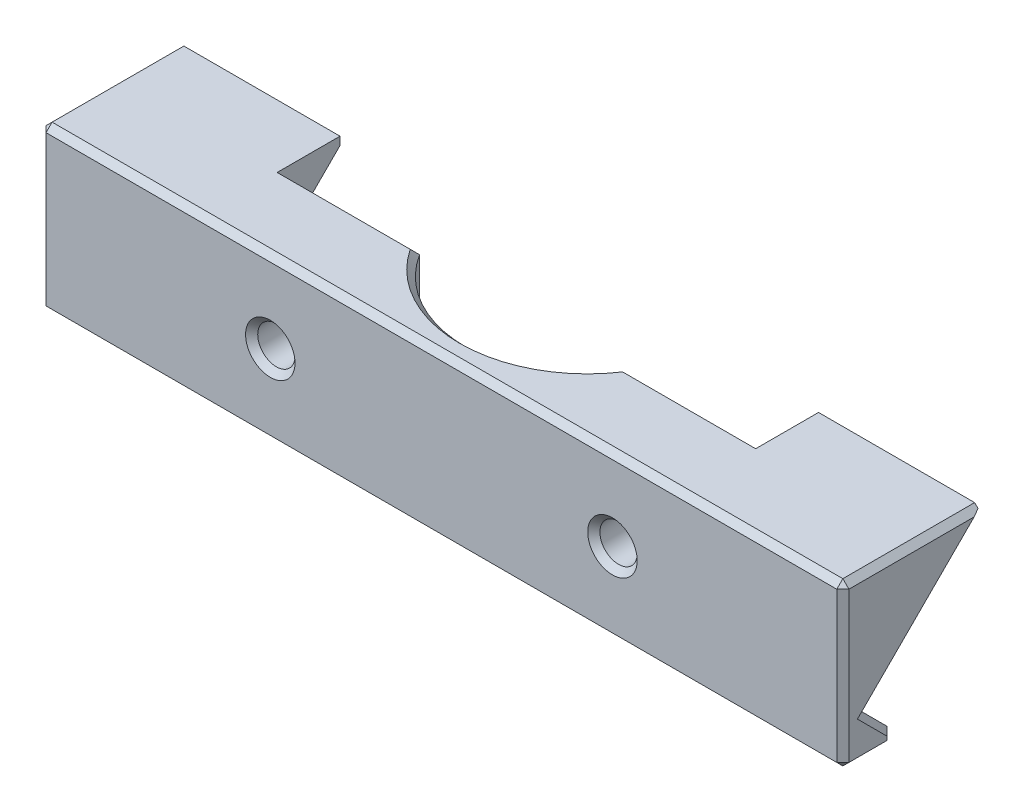
SolidWorks part; units mm, degrees
ref_plane "Front" through (0, 0, 0) normal (0, 0, 1) x (1, 0, 0)
ref_plane "Top" through (0, 0, 0) normal (0, 1, 0) x (1, 0, 0)
ref_plane "Right" through (0, 0, 0) normal (1, 0, 0) x (0, 0, -1)
sketch "Skizze1" plane through (0, 0, 0) normal (0, 0, 1) x (1, 0, 0)
  line L0 (0, 0) -> (0, 36.2286) construction
  line L1 (29.5, 0) -> (-29.5, 0)
  line L2 (-29.5, 0) -> (-29.5, 20)
  line L3 (-29.5, 20) -> (29.5, 20)
  line L4 (29.5, 0) -> (29.5, 20)
  point P7 (0, 20)
  dimension "D1" = 20
  dimension "D2" = 59
extrude "Aufsatz-Linear austragen1" add sketch "Skizze1" along normal blind 10
sketch "Skizze2" plane through (-29.5, 0, 0) normal (-1, 0, 0) x (0, 0, 1)
  line L1 (7.1421, 4.8579) -> (-7, 19)
  line L5 (0, 20) -> (10, 20)
  line L6 (10, 20) -> (0, 20) construction
  line L7 (10, 20) -> (10, 0)
  line L8 (10, 0) -> (2.2843, 0)
  line L9 (10, 0) -> (0, 0) construction
  line L10 (2.2843, 0) -> (7.1421, 4.8579)
  line L15 (-7, 19) -> (-7, 20)
  line L16 (142, 20) -> (-158, 20) construction
  line L17 (-7, 20) -> (0, 20)
  line L18 (7.1421, 4.8579) -> (-63.5685, -65.8528) construction
extrude "Aufsatz-Linear austragen2" add sketch "Skizze2" along normal blind 20
mirror "Spiegeln1" about plane through (0, 0, 0) normal (1, 0, 0) of "Aufsatz-Linear austragen2"
sketch "Skizze3" plane through (0, 0, 0) normal (0, -1, 0) x (1, 0, 0)
  line L0 (0, 0) -> (0, -17.264) construction
  circle A0 centre (0, -8) radius 15
  dimension "D1" = 30
extrude "Schnitt-Linear austragen1" cut sketch "Skizze3" against normal blind 20
sketch "Skizze4" plane through (0, 0, 0) normal (0, 0, -1) x (-1, 0, 0)
  line L0 (-12.6886, 10) -> (-29.5, 10) construction
  line L1 (-12.6886, 0) -> (-12.6886, 20) construction
  line L2 (-29.5, 12) -> (-29.5, 4.8579) construction
  line L3 (0, 0) -> (0, 20) construction
  line L4 (12.6886, 20) -> (-12.6886, 20) construction
  circle A0 centre (-21.0943, 10) radius 2.3
  circle A1 centre (21.0943, 10) radius 2.3
  dimension "D1" = 4.6
extrude "Schnitt-Linear austragen2" cut sketch "Skizze4" against normal blind 10
sketch "Skizze5" plane through (0, 0, 0) normal (0, 0, -1) x (-1, 0, 0)
  circle A0 centre (-21.0943, 10) radius 3.75
  circle A1 centre (21.0943, 10) radius 3.75
  dimension "D1" = 7.5
extrude "Schnitt-Linear austragen3" cut sketch "Skizze5" against normal blind 3
sketch "Skizze6" plane through (49.5, 0, 0) normal (1, 0, 0) x (0, 0, -1)
  line L0 (-3.7843, 1.5) -> (-3.7843, 0)
  line L1 (-7.1421, 4.8579) -> (-2.2843, 0) construction
  line L2 (-2.2843, 0) -> (-10, 0) construction
  line L3 (-3.7843, 0) -> (-1.8311, -0.9493)
  line L4 (-1.8311, -0.9493) -> (-1.3963, 1.5278)
  line L5 (-1.3963, 1.5278) -> (-3.7843, 1.5)
  dimension "D1" = 1.5
extrude "Schnitt-Linear austragen4" cut sketch "Skizze6" against normal blind 20
mirror "Spiegeln2" about plane through (0, 0, 0) normal (1, 0, 0) of "Schnitt-Linear austragen4"
chamfer "Fase1" distance 0.75 angle 45 26 edges at (-18.7943, 10, 10) (18.7943, 10, 10) (49.5, 20, 1.5) (49.5, 11.9289, 0.0711) (49.5, 3.1789, 5.4632) (49.5, 0.75, 3.7843) (-49.5, 0, 6.8921) (49.5, 10, 10) (0, 20, 10) (-49.5, 10, 10) (0, 0, 10) (49.5, 0, 6.8921) (39.5, 0, 3.7843) (29.5, 0, 1.8921) (21.0943, 0, 0) (0, 0, 7) (-21.0943, 0, 0) (-29.5, 0, 1.8921) (-39.5, 0, 3.7843) (-49.5, 0.75, 3.7843) (-49.5, 3.1789, 5.4632) (-49.5, 11.9289, 0.0711) (-21.0943, 20, 0) (0, 20, 7) (21.0943, 20, 0) (-49.5, 20, 1.5)
fillet "Verrundung1" radius 2 2 edges at (29.5, 15.625, 0) (-29.5, 15.625, 0)
